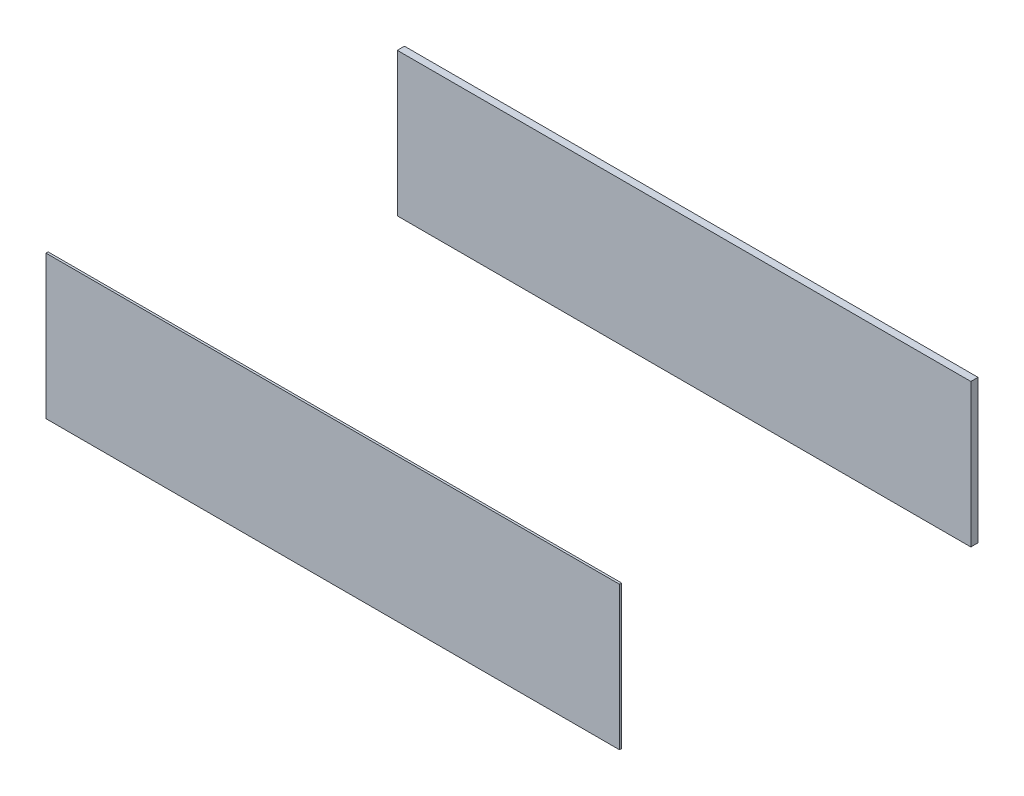
SolidWorks part; units mm, degrees
ref_plane "Front Plane" through (0, 0, 0) normal (0, 0, 1) x (1, 0, 0)
ref_plane "Top Plane" through (0, 0, 0) normal (0, 1, 0) x (1, 0, 0)
ref_plane "Right Plane" through (0, 0, 0) normal (1, 0, 0) x (0, 0, -1)
sketch "Sketch3" plane through (0, 0, 0) normal (0, 1, 0) x (1, 0, 0)
  line L1 (-39.8113, 2.7358) -> (40.1887, 2.7358)
  line L2 (-39.8113, 2.7358) -> (-39.8113, 1.7358)
  line L3 (-39.8113, 1.7358) -> (40.1887, 1.7358)
  line L4 (40.1887, 2.7358) -> (40.1887, 1.7358)
  line L5 (-39.8113, -47.2642) -> (40.1887, -47.2642)
  line L6 (-39.8113, -47.2642) -> (-39.8113, -46.9642)
  line L7 (-39.8113, -46.9642) -> (40.1887, -46.9642)
  line L8 (40.1887, -47.2642) -> (40.1887, -46.9642)
  dimension "D1" = 80
  dimension "D2" = 1
  dimension "D3" = 0.3
  dimension "D4" = 50
extrude "Boss-Extrude1" add sketch "Sketch3" along normal blind 20
